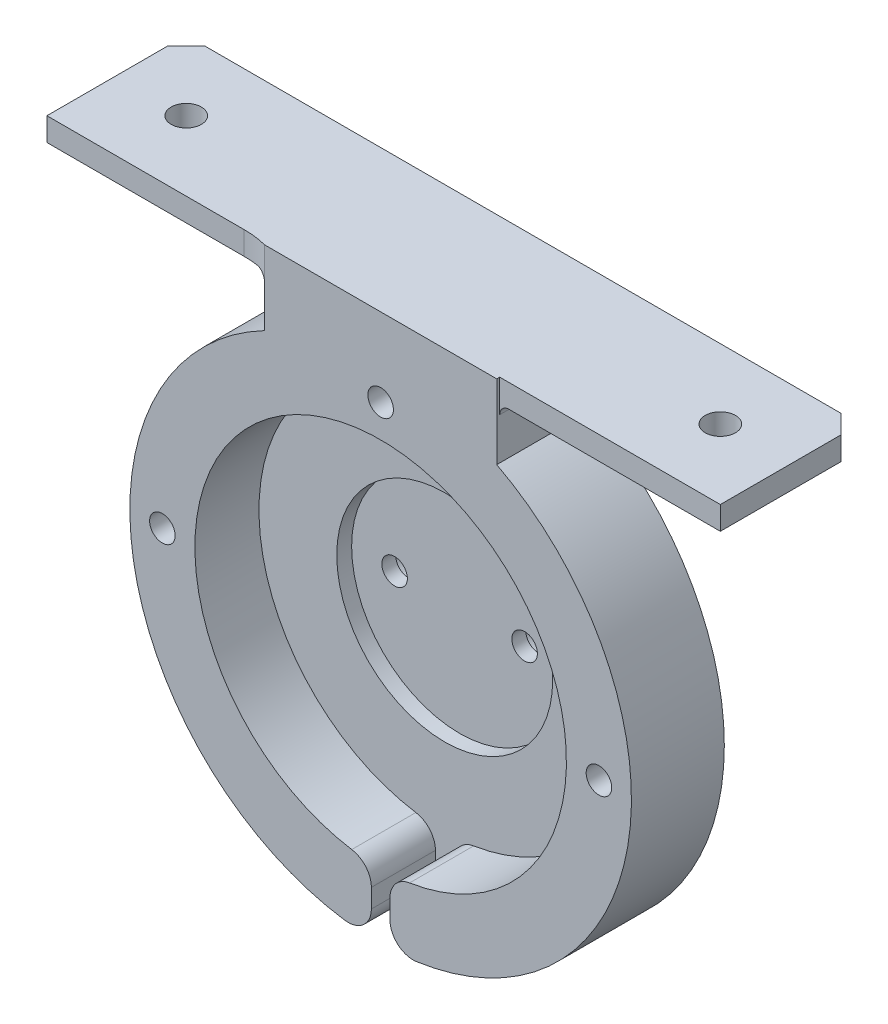
SolidWorks part; units mm, degrees
ref_plane "Front Plane" through (0, 0, 0) normal (0, 0, 1) x (1, 0, 0)
ref_plane "Top Plane" through (0, 0, 0) normal (0, 1, 0) x (1, 0, 0)
ref_plane "Right Plane" through (0, 0, 0) normal (1, 0, 0) x (0, 0, -1)
sketch "Sketch1" plane through (0, 0, 0) normal (0, 0, 1) x (1, 0, 0)
  circle A0 centre (0, 0) radius 27
  circle A1 centre (0, 0) radius 23.5 construction
  circle A2 centre (0, 23.5) radius 1.375
  circle A3 centre (23.5, 0) radius 1.375
  circle A4 centre (0, -23.5) radius 1.375 construction
  circle A5 centre (-23.5, 0) radius 1.375
  circle A6 centre (0, 0) radius 20
  point P15 (0, 0)
  dimension "D1" = 54
  dimension "D2" = 47
  dimension "D3" = 2.75
  dimension "D5" = 40
  dimension "D4" = 4
extrude "Boss-Extrude1" add sketch "Sketch1" along normal blind 10
sketch "Sketch3" plane through (0, 0, 0) normal (0, 0, 1) x (1, 0, 0)
  circle A0 centre (0, 0) radius 20
  circle A1 centre (0, 0) radius 7 construction
  circle A2 centre (-7, 0) radius 1.375
  circle A3 centre (7, 0) radius 1.375
  circle A4 centre (0, 0) radius 11.5 construction
  dimension "D1" = 40
  dimension "D2" = 14
  dimension "D3" = 2.75
  dimension "D4" = 23
extrude "Boss-Extrude2" add sketch "Sketch3" along normal blind 1.5
sketch "Sketch5" plane through (0, 0, 10) normal (0, 0, 1) x (1, 0, 0)
  line L0 (0, -5.5) -> (0, 5.5) construction
  line L1 (-12.5, 23.9322) -> (-4.2519, 23.9322)
  line L2 (-12.5, 23.9322) -> (-12.5, 31.9322)
  line L3 (-12.5, 31.9322) -> (12.5, 31.9322)
  line L4 (12.5, 23.9322) -> (12.5, 31.9322)
  line L5 (4.2678, 23.9322) -> (0, 26.2545)
  line L6 (0, 26.2545) -> (-4.2519, 23.9322)
  line L7 (4.2678, 23.9322) -> (12.5, 23.9322)
  circle A0 centre (0, 0) radius 27 construction
  dimension "D1" = 12.5
  dimension "D2" = 25
  dimension "D3" = 8
extrude "Boss-Extrude3" add sketch "Sketch5" against normal blind 6
sketch "Sketch6" plane through (0, 31.9322, 0) normal (0, 1, 0) x (1, 0, 0)
  line L0 (12.5, -4) -> (12.5, -10) construction
  line L1 (-12.5, -10) -> (12.5, -10)
  line L2 (-12.5, -10) -> (-12.5, 5.32)
  line L3 (-12.5, 5.32) -> (12.5, 5.32)
  line L4 (12.5, -10) -> (12.5, 5.32)
  dimension "D1" = 15.32
extrude "Boss-Extrude4" add sketch "Sketch6" against normal blind 2.5
sketch "Sketch7" plane through (0, 31.9322, 0) normal (0, 1, 0) x (1, 0, 0)
  line L0 (0, -5.5) -> (0, 5.5) construction
  line L1 (-36.25, -67.18) -> (36.25, -67.18) construction
  line L2 (-36.25, -67.18) -> (-36.25, 1.32) construction
  line L3 (-32.25, 5.32) -> (32.25, 5.32) construction
  line L4 (36.25, -67.18) -> (36.25, 1.32) construction
  line L5 (-28.75, -9.68) -> (-36.25, -9.68)
  line L6 (0, 5.32) -> (-36.25, 5.32)
  line L7 (-36.25, -9.68) -> (-36.25, -2.18)
  line L8 (12.5, -4) -> (-12.5, -4) construction
  line L9 (0, 5.32) -> (0, -9.68)
  line L10 (0, -9.68) -> (-28.75, -9.68)
  line L11 (-36.25, 5.32) -> (-36.25, -2.18)
  arc A0 (32.25, 5.32) -> (36.25, 1.32) centre (32.25, 1.32) cw construction
  circle A3 centre (-28.75, -2.18) radius 1.625
  point P4 (0, 5.32)
  point P11 (36.25, 5.32)
  point P14 (-36.25, 5.32)
  point P21 (-36.25, -9.68)
  dimension "D4" = 4
  dimension "D7" = 3.25
  dimension "D1" = 72.5
  dimension "D2" = 72.5
  dimension "D3" = 9.32
  dimension "D5" = 15
extrude "Boss-Extrude5" add sketch "Sketch7" against normal blind 2.5 contours L10 L9 L6 L11 A3 region at (-17.9604, 31.9322, 2.18)
fillet "Fillet2" radius 10 1 edges at (-12.5, 30.6822, 9.68)
sketch "Sketch8" plane through (0, 31.9322, 0) normal (0, 1, 0) x (1, 0, 0)
  circle A0 centre (-28.75, -2.18) radius 2.5
  circle A1 centre (-28.75, -2.18) radius 4
  dimension "D1" = 5
  dimension "D2" = 8
extrude "Boss-Extrude6" [suppressed] add sketch "Sketch8" against normal blind 5
mirror "Mirror1" about plane through (0, 0, 0) normal (1, 0, 0) of "Boss-Extrude4", "Boss-Extrude5", "Boss-Extrude6"
fillet "Fillet3" radius 1 3 edges at (0, 29.4322, 4) (12.5, 29.4322, 6.84) (-12.5, 29.4322, 7)
fillet "Fillet4" [suppressed] radius 10
chamfer "Chamfer1" distance 2 angle 45 2 edges at (-36.25, 30.6822, -5.32) (36.25, 30.6822, -5.32)
sketch "Sketch14" plane through (0, 0, 1.5) normal (0, 0, 1) x (1, 0, 0)
  circle A0 centre (0, 0) radius 11.625
  circle A1 centre (0, 0) radius 20
  dimension "D1" = 23.25
extrude "Boss-Extrude10" add sketch "Sketch14" along normal blind 1.6
sketch "Sketch9" plane through (0, 0, 1.5) normal (0, 0, 1) x (1, 0, 0)
  circle A0 centre (0, 0) radius 12
  circle A1 centre (0, 0) radius 20
  dimension "D1" = 24
extrude "Boss-Extrude7" [suppressed] add sketch "Sketch9" along normal up to surface (8.5 mm away) up to face at (-2.5, 17.8458, 10)
sketch "Sketch4" plane through (0, 0, 0) normal (0, 1, 0) x (1, 0, 0)
  line L0 (12.5, -10) -> (-12.5, -10) construction
  line L1 (-1, -3.1) -> (1, -3.1)
  line L2 (-1, -3.1) -> (-1, -10)
  line L3 (-1, -10) -> (1, -10)
  line L4 (1, -3.1) -> (1, -10)
  line L6 (-11.625, -3.1) -> (11.625, -3.1) construction
  point P7 (0, -3.1)
  dimension "D2" = 2
extrude "Cut-Extrude1" cut sketch "Sketch4" against normal up to surface (26.9815 mm away) up to face at (0, 11.9661, 7)
fillet "Fillet6" [suppressed] radius 2
sketch "Sketch10" [suppressed] plane through (0, 0, 10) normal (0, 0, 1) x (1, 0, 0)
  line L0 (-4.25, -19.5432) -> (-4.25, -13.8632)
  line L1 (-1.75, -24.7171) -> (-1.75, -13.4884) construction
  line L2 (0, -8.4586) -> (0, 8.4586) construction
  line L3 (4.25, -19.5432) -> (4.25, -13.8632)
  arc A0 (4.25, -19.5432) -> (-4.25, -19.5432) centre (0, 0) ccw
  arc A1 (-12.5, 23.9322) -> (-4.05, -26.6945) centre (0, 0) ccw construction
  arc A2 (4.25, -13.8632) -> (-4.25, -13.8632) centre (0, 0) ccw
  circle A3 centre (0, 0) radius 12 construction
  dimension "D1" = 7
  dimension "D2" = 2.5
  dimension "D3" = 2.5
extrude "Cut-Extrude2" [suppressed] cut sketch "Sketch10" against normal up to surface (6.5 mm away) up to face at (0, -13.4891, 3.1)
sketch "Sketch12" plane through (0, 0, 0) normal (0, 0, -1) x (-1, 0, 0)
  line L2 (0, 8.4586) -> (0, -8.4586) construction
  line L3 (-3.75, 5.6125) -> (-2.6485, 4.2998)
  line L4 (8.4586, 0) -> (-8.4586, 0) construction
  line L5 (3.75, 5.6125) -> (2.6485, 4.2998)
  arc A0 (2.6485, 4.2998) -> (-2.6485, 4.2998) centre (0, 0) ccw construction
  arc A1 (-2.6485, 4.2998) -> (2.6485, 4.2998) centre (0, 0) cw
  circle A2 centre (0, 0) radius 6.75 construction
  arc A3 (3.75, 5.6125) -> (-3.75, 5.6125) centre (0, 0) ccw
  circle A4 centre (0, 0) radius 5.05 construction
  dimension "D1" = 10.1
  dimension "D2" = 13.5
  dimension "D3" = 3.75
  dimension "D4" = 3.75
  dimension "D5" = 50
  dimension "D6" = 50
extrude "Boss-Extrude8" [suppressed] add sketch "Sketch12" along normal blind 4.5
fillet "Fillet7" [suppressed] radius 1
sketch "Sketch13" plane through (0, 0, 0) normal (0, 0, -1) x (-1, 0, 0)
  circle A0 centre (0, 0) radius 2.5
  dimension "D1" = 5
extrude "Boss-Extrude9" add sketch "Sketch13" along normal blind 4.5
fillet "Fillet9" radius 2.5 4 edges at (1, -26.9815, 6.55) (-1, -26.9815, 6.55) (-1, -19.975, 6.55) (1, -19.975, 6.55)
sketch "Sketch15" plane through (0, 0, 0) normal (0, 0, -1) x (-1, 0, 0)
  circle A0 centre (0, 0) radius 12.5
  dimension "D1" = 25
extrude "Boss-Extrude11" add sketch "Sketch15" along normal blind 1.95
sketch "Sketch16" plane through (0, 0, -1.95) normal (0, 0, -1) x (-1, 0, 0)
  circle A0 centre (7, 0) radius 2.5
  circle A1 centre (-7, 0) radius 2.5
  dimension "D1" = 5
extrude "Cut-Extrude3" cut sketch "Sketch16" against normal up to surface (1.95 mm away) up to face at (12.5, 0, 0)
